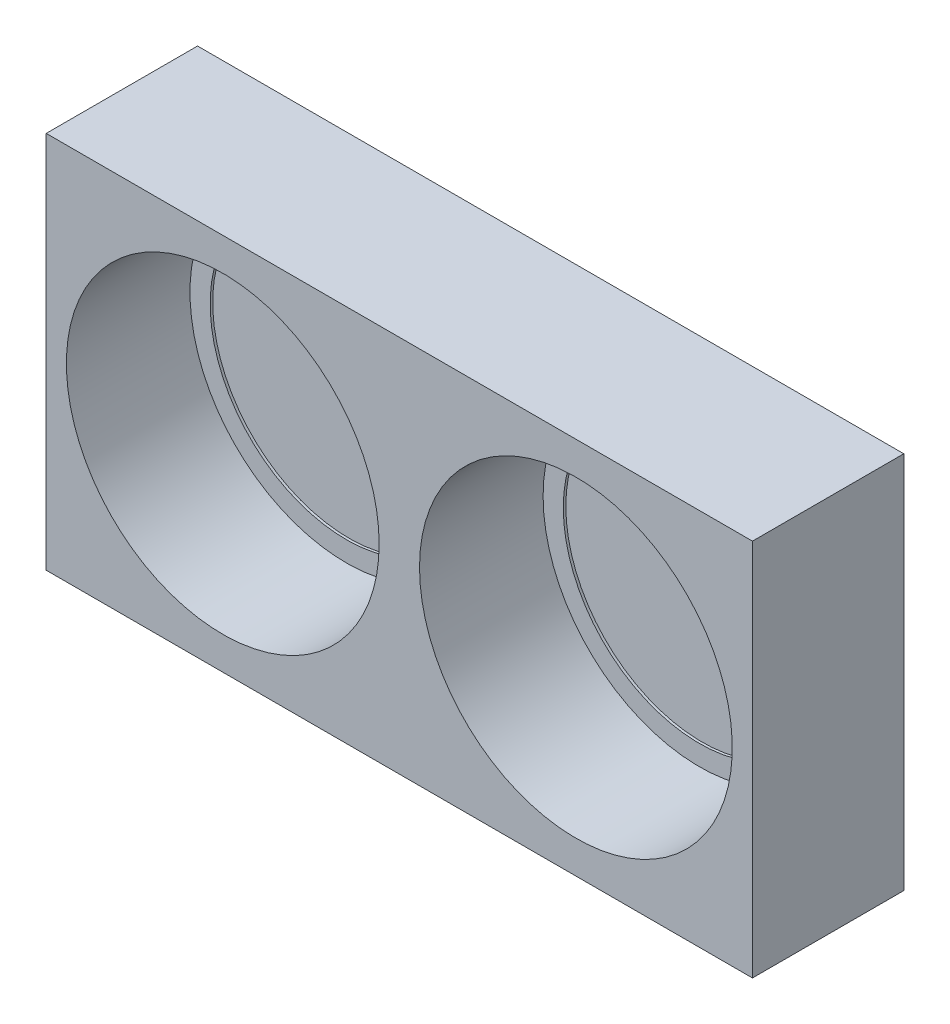
SolidWorks part; units mm, degrees
ref_plane "Plan de face" through (0, 0, 0) normal (0, 0, 1) x (1, 0, 0)
ref_plane "Plan de dessus" through (0, 0, 0) normal (0, 1, 0) x (1, 0, 0)
ref_plane "Plan de droite" through (0, 0, 0) normal (1, 0, 0) x (0, 0, -1)
sketch "Esquisse1" plane through (0, 0, 0) normal (0, 0, 1) x (1, 0, 0)
  line L1 (0, 0) -> (140, 0)
  line L2 (0, 0) -> (0, 75)
  line L3 (0, 75) -> (140, 75)
  line L4 (140, 0) -> (140, 75)
  dimension "D1" = 75
  dimension "D2" = 140
extrude "Boss.-Extru.1" add sketch "Esquisse1" along normal blind 30
sketch "Esquisse2" plane through (0, 0, 30) normal (0, 0, 1) x (1, 0, 0)
  line L0 (70, 0) -> (70, 75) construction
  line L1 (0, 0) -> (140, 0) construction
  line L2 (140, 75) -> (0, 75) construction
  line L3 (35, 37.5) -> (70, 37.5) construction
  circle A0 centre (35, 37.5) radius 31
  circle A1 centre (105, 37.5) radius 31
  dimension "D1" = 62
  dimension "D2" = 35
extrude "Enlèv. mat.-Extru.1" cut sketch "Esquisse2" against normal blind 25
sketch "Esquisse3" plane through (0, 0, 5) normal (0, 0, 1) x (1, 0, 0)
  line L0 (70, 0) -> (70, 75) construction
  line L1 (0, 0) -> (140, 0) construction
  line L2 (140, 75) -> (0, 75) construction
  circle A0 centre (35, 37.5) radius 3.4
  circle A1 centre (35, 37.5) radius 31 construction
  circle A2 centre (105, 37.5) radius 3.4
  dimension "D1" = 6.8
extrude "Enlèv. mat.-Extru.2" cut sketch "Esquisse3" against normal through all both and the other way through all
sketch "Esquisse4" plane through (0, 0, 5) normal (0, 0, 1) x (1, 0, 0)
  line L0 (70, 0) -> (70, 75) construction
  line L1 (0, 0) -> (140, 0) construction
  line L2 (140, 75) -> (0, 75) construction
  circle A0 centre (35, 37.5) radius 31
  circle A1 centre (35, 37.5) radius 27
  circle A2 centre (105, 37.5) radius 27
  circle A3 centre (105, 37.5) radius 31
  dimension "D1" = 54
  dimension "D2" = 62
extrude "Boss.-Extru.2" add sketch "Esquisse4" along normal blind 0.5
